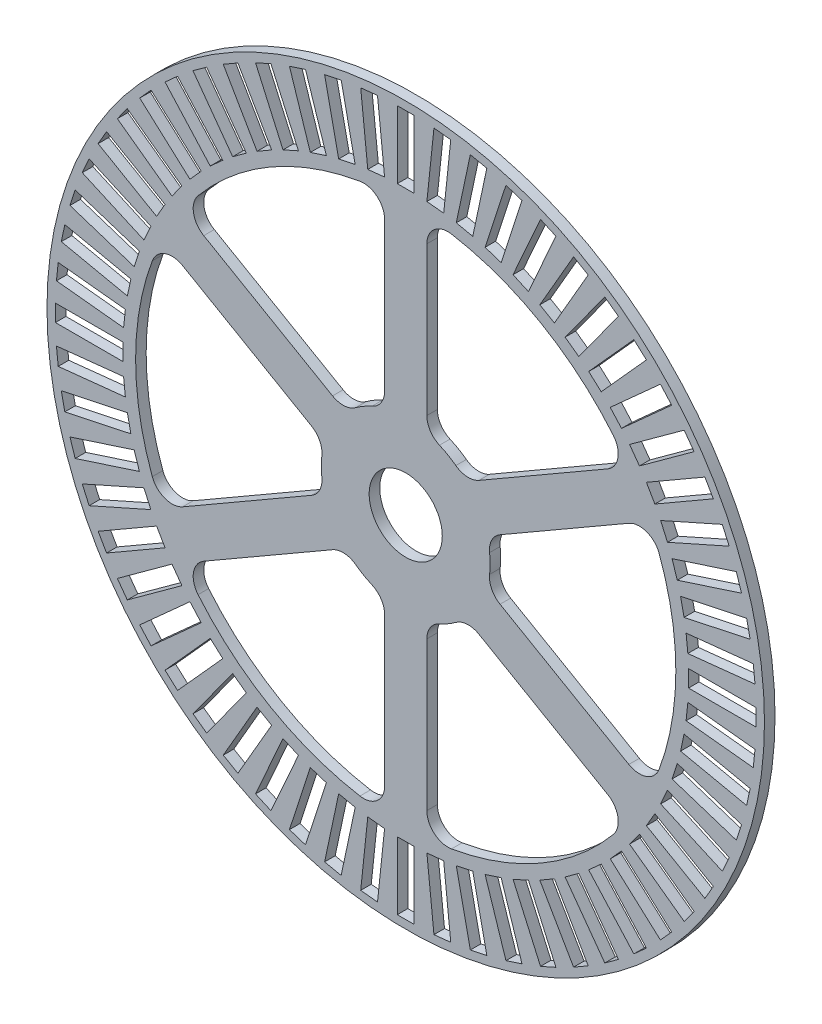
SolidWorks part; units mm, degrees
material "1023 Carbon Steel Sheet (SS)"
ref_plane "Front Plane" through (0, 0, 0) normal (0, 0, 1) x (1, 0, 0)
ref_plane "Top Plane" through (0, 0, 0) normal (0, 1, 0) x (1, 0, 0)
ref_plane "Right Plane" through (0, 0, 0) normal (1, 0, 0) x (0, 0, -1)
sketch "Sketch1" plane through (0, 0, 0) normal (0, 0, 1) x (1, 0, 0)
  circle A0 centre (0, 0) radius 40.64
  circle A1 centre (0, 0) radius 53.975
  dimension "D1" = 107.95
  dimension "D2" = 13.335
extrude "Boss-Extrude1" add sketch "Sketch1" along normal blind 1.5875
sketch "Sketch4" plane through (0, 0, 1.5875) normal (0, 0, 1) x (1, 0, 0)
  line L1 (-1.27, 52.705) -> (1.27, 52.705)
  line L2 (-1.27, 52.705) -> (-1.27, 42.545)
  line L3 (-1.27, 42.545) -> (1.27, 42.545)
  line L4 (1.27, 52.705) -> (1.27, 42.545)
  line L5 (-1.27, 52.705) -> (1.27, 42.545) construction
  line L6 (-1.27, 42.545) -> (1.27, 52.705) construction
  point P0 (0, 47.625)
  dimension "D1" = 2.54
  dimension "D2" = 10.16
  dimension "D3" = 47.625
extrude "Cut-Extrude3" cut sketch "Sketch4" against normal blind 5.08 contours L1 L4 L3 L2
pattern_circular "CirPattern2" count 60 over 360 of "Cut-Extrude3"
sketch "Sketch7" plane through (0, 0, 0) normal (0, 0, -1) x (-1, 0, 0)
  line L0 (-1.905, 0) -> (49998.095, 0) construction
  circle A2 centre (60.325, 0) radius 6.985
  point P6 (60.325, 0)
  dimension "D1" = 60.325
  dimension "D2" = 13.97
extrude "Cut-Extrude5" [suppressed] cut sketch "Sketch7" against normal blind 2.54
pattern_circular "CirPattern4" [suppressed] count 6 over 360 of bodies 110
sketch "Sketch8" plane through (0, 0, 0) normal (0, 0, 1) x (1, 0, 0)
  line L0 (-3.175, 12.2967) -> (-3.175, 40.5158)
  line L1 (3.175, 12.2967) -> (3.175, 40.5158)
  line L2 (9.0618, 8.898) -> (33.5002, 23.0075)
  line L3 (12.2368, 3.3987) -> (36.6752, 17.5083)
  line L4 (12.2368, -3.3987) -> (36.6752, -17.5083)
  line L5 (9.0618, -8.898) -> (33.5002, -23.0075)
  line L6 (3.175, -12.2967) -> (3.175, -40.5158)
  line L7 (-3.175, -12.2967) -> (-3.175, -40.5158)
  line L8 (-9.0618, -8.898) -> (-33.5002, -23.0075)
  line L9 (-12.2368, -3.3987) -> (-36.6752, -17.5083)
  line L10 (-12.2368, 3.3987) -> (-36.6752, 17.5083)
  line L11 (-9.0618, 8.898) -> (-33.5002, 23.0075)
  circle A1 centre (0, 0) radius 40.64 construction
  arc A2 (-33.5002, 23.0075) -> (-36.6752, 17.5083) centre (0, 0) ccw
  arc A3 (-36.6752, -17.5083) -> (-33.5002, -23.0075) centre (0, 0) ccw
  arc A4 (-3.175, -40.5158) -> (3.175, -40.5158) centre (0, 0) ccw
  arc A5 (33.5002, -23.0075) -> (36.6752, -17.5083) centre (0, 0) ccw
  arc A6 (36.6752, 17.5083) -> (33.5002, 23.0075) centre (0, 0) ccw
  arc A7 (3.175, 40.5158) -> (-3.175, 40.5158) centre (0, 0) ccw
  circle A8 centre (0, 0) radius 5.5
  arc A9 (-12.2368, 3.3987) -> (-12.2368, -3.3987) centre (0, 0) ccw
  arc A10 (-3.175, 12.2967) -> (-9.0618, 8.898) centre (0, 0) ccw
  arc A11 (9.0618, 8.898) -> (3.175, 12.2967) centre (0, 0) ccw
  arc A12 (12.2368, -3.3987) -> (12.2368, 3.3987) centre (0, 0) ccw
  arc A13 (3.175, -12.2967) -> (9.0618, -8.898) centre (0, 0) ccw
  arc A14 (-9.0618, -8.898) -> (-3.175, -12.2967) centre (0, 0) ccw
  point P32 (0, 0)
  dimension "D1" = 11
  dimension "D4" = 25.4
  dimension "D2" = 6.35
  dimension "D3" = 6
extrude "Boss-Extrude2" add sketch "Sketch8" along normal blind 1.5875
fillet "Fillet1" radius 3.175 24 edges at (12.2368, -3.3987, 0.7937) (12.2368, 3.3987, 0.7937) (9.0618, -8.898, 0.7937) (3.175, -12.2967, 0.7937) (-3.175, -12.2967, 0.7937) (-9.0618, -8.898, 0.7937) (-12.2368, 3.3987, 0.7937) (-12.2368, -3.3987, 0.7937) (-3.175, 12.2967, 0.7937) (-9.0618, 8.898, 0.7937) (3.175, 12.2967, 0.7937) (9.0618, 8.898, 0.7937) (3.175, 40.5158, 0.7937) (33.5002, 23.0075, 0.7937) (36.6752, 17.5083, 0.7937) (36.6752, -17.5083, 0.7937) (33.5002, -23.0075, 0.7937) (3.175, -40.5158, 0.7937) (-3.175, -40.5158, 0.7937) (-33.5002, -23.0075, 0.7937) (-36.6752, -17.5083, 0.7937) (-36.6752, 17.5083, 0.7937) (-33.5002, 23.0075, 0.7937) (-3.175, 40.5158, 0.7937)
